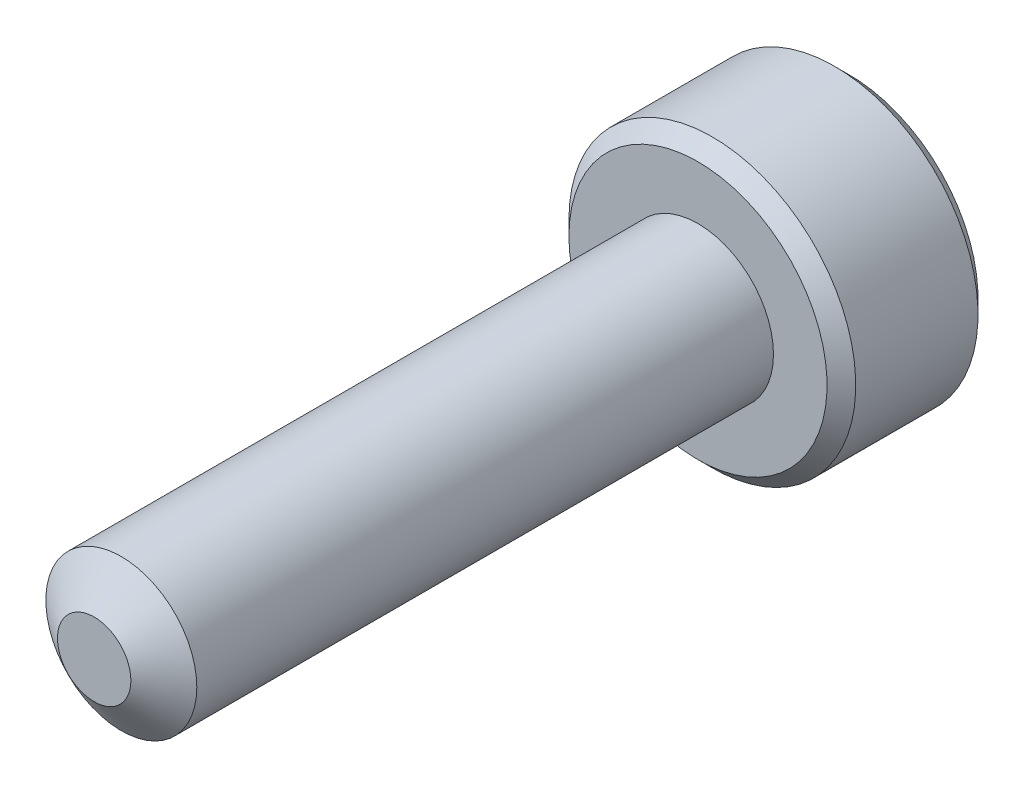
SolidWorks part; units mm, degrees
other "DetailItem1"
ref_plane "Front Plane" through (0, 0, 0) normal (0, 0, 1) x (1, 0, 0)
ref_plane "Top Plane" through (0, 0, 0) normal (0, 1, 0) x (1, 0, 0)
ref_plane "Right Plane" through (0, 0, 0) normal (1, 0, 0) x (0, 0, -1)
sketch "Sketch1" plane through (0, 0, 0) normal (0, 0, 1) x (1, 0, 0)
  circle A0 centre (0, 0) radius 1
  dimension "OD" = 2
extrude "Extrude1" add sketch "Sketch1" against normal blind 8
sketch "Sketch2" plane through (0, 0, 0) normal (0, 0, 1) x (1, 0, 0)
  circle A0 centre (0, 0) radius 1 construction
  circle A1 centre (0, 0) radius 1
curve "Helix/Spiral1" pitch 0.4 height 8.4 turns 21 parameters "pitch"=0.4
sketch "Sketch3" plane through (0, 0, 0) normal (1, 0, 0) x (0, 0, -1)
  line L0 (-0.35, 1) -> (-0.2, 0.7402)
  line L1 (-0.2, 0.7402) -> (-0.15, 0.7402)
  line L2 (-0.15, 0.7402) -> (0, 1)
  line L3 (-0.35, 1) -> (0, 1)
  line L4 (-0.175, 1) -> (-0.175, 0.7402) construction
  line L5 (-0.275, 0.8701) -> (-0.075, 0.8701) construction
  line L6 (0, 1) -> (0, -1) construction
  dimension "D1" = 0.05
  dimension "D2" = 0.2
  dimension "D3" = 60
sweep "Cut-Sweep1" [suppressed] cut profiles "Sketch3" path "Helix/Spiral1"
sketch "Sketch4" plane through (0, 0, 0) normal (1, 0, 0) x (0, 0, -1)
  line L0 (0.3598, 1) -> (0, 0.4862)
  line L1 (0, 0.4862) -> (0, 1)
  line L2 (0.3598, 1) -> (0, 1)
  line L3 (-0.35, 1) -> (0, 1) construction
  line L4 (0, 0) -> (7.0209, 0) construction
  dimension "D1" = 55
  dimension "D2" = 0.254
revolve "Cut-Revolve1" cut sketch "Sketch4" angle 360 about L4
sketch "Sketch6" plane through (0, 0, -8) normal (0, 0, -1) x (-1, 0, 0)
  circle A0 centre (0, 0) radius 1.9
  dimension "head dia" = 3.8
extrude "Extrude2" add sketch "Sketch6" along normal blind 2
sketch "Sketch7" plane through (0, 0, -10) normal (0, 0, -1) x (-1, 0, 0)
  line L1 (0, 0.866) -> (-0.75, 0.433)
  line L2 (-0.75, 0.433) -> (-0.75, -0.433)
  line L3 (-0.75, -0.433) -> (0, -0.866)
  line L4 (0, -0.866) -> (0.75, -0.433)
  line L5 (0.75, -0.433) -> (0.75, 0.433)
  line L6 (0.75, 0.433) -> (0, 0.866)
  circle A0 centre (0, 0) radius 0.75 construction
  dimension "hex dia" = 1.5
extrude "Cut-Extrude1" cut sketch "Sketch7" against normal blind 1.125
sketch "Sketch8" plane through (0, 0, -10) normal (0, 0, -1) x (-1, 0, 0)
  circle A0 centre (0, 0) radius 0.866
extrude "Cut-Extrude2" cut sketch "Sketch8" against normal through all draft 45
chamfer "Chamfer1" distance 0.19 angle 45 2 edges at (-1.9, 0, -10) (-1.9, 0, -8)
sketch "Sketch10" plane through (0, 0, -8) normal (0, 0, 1) x (1, 0, 0)
  circle A1 centre (0, 0) radius 1
  circle A2 centre (0, 0) radius 1
  dimension "D1" = 0
ref_plane "Plane1" through (0, 0, 0) normal (0, 0, 1) x (1, 0, 0)
extrude "partial thread" [suppressed] add sketch "Sketch10" along normal up to surface (2 mm away) separate body
chamfer "Chamfer2" [suppressed] distance 0.04 angle 45
combine bodies "Combine1" [suppressed] operation type add bodies to combine 107 108
sketch "Sketch9" plane through (0, 0, 0) normal (1, 0, 0) x (0, 0, -1)
  line L0 (0, 1) -> (0, -1) construction
  line L1 (1, 1) -> (1, -1) construction
  dimension "D1" = 1
equation "\"D3@Helix/Spiral1\" = \"screw length@Extrude1\"+\"pitch@Helix/Spiral1\""
equation "\"D1@Sketch3\" = \"pitch@Helix/Spiral1\"*.125"
equation "\"D2@Sketch3\" = \"pitch@Helix/Spiral1\"*.5"
equation "\"D1@Cut-Extrude1\" = \"hex dia@Sketch7\"*.75"
equation "\"D1@Chamfer1\" = \"head dia@Sketch6\"*.05"
equation "\"D1@Sketch9\" = \"pitch@Helix/Spiral1\"*2.5"
equation "\"D1@Chamfer2\"=\"OD@Sketch1\"*.02"
